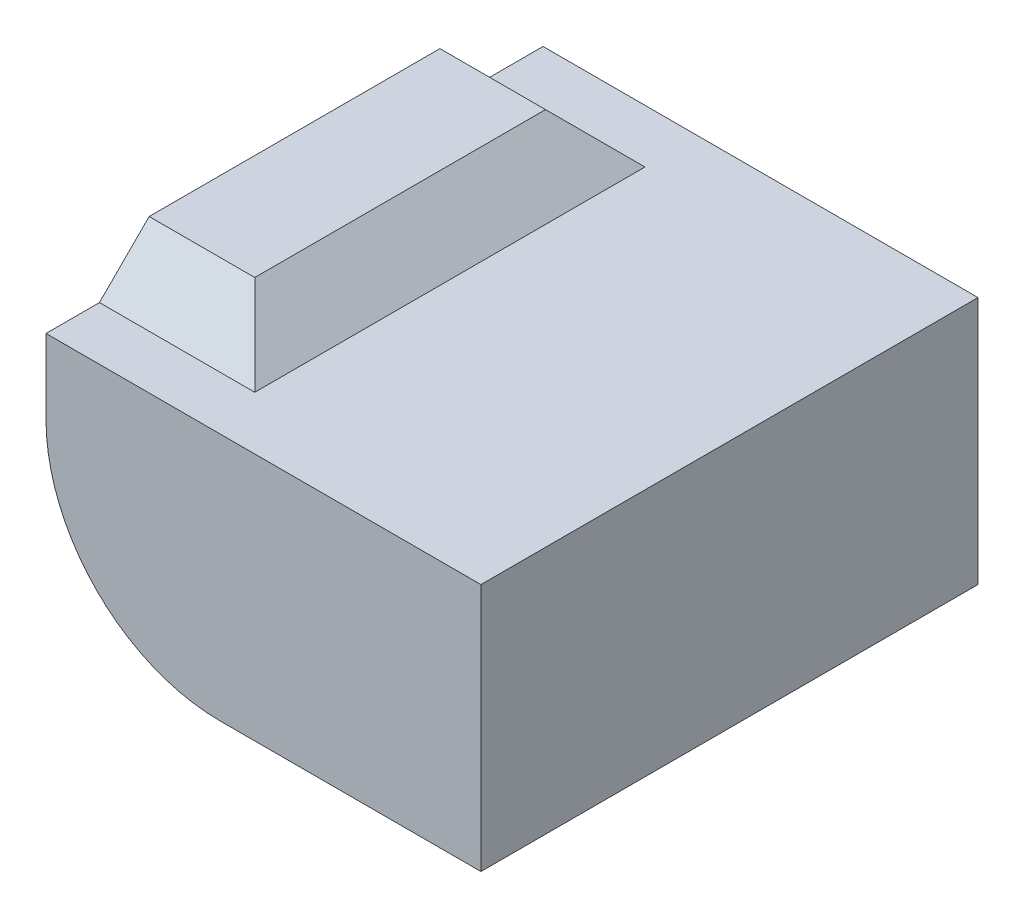
SolidWorks part; units mm, degrees
ref_plane "Front Plane" through (0, 0, 0) normal (0, 0, 1) x (1, 0, 0)
ref_plane "Top Plane" through (0, 0, 0) normal (0, 1, 0) x (1, 0, 0)
ref_plane "Right Plane" through (0, 0, 0) normal (1, 0, 0) x (0, 0, -1)
sketch "Sketch1" plane through (0, 0, 0) normal (0, 0, 1) x (1, 0, 0)
  line L1 (-175, -150) -> (175, -150)
  line L2 (-175, -150) -> (-175, 150)
  line L3 (-175, 150) -> (175, 150)
  line L4 (175, -150) -> (175, 150)
  line L5 (-175, -150) -> (175, 150) construction
  line L6 (-175, 150) -> (175, -150) construction
  point P0 (0, 0)
  dimension "D1" = 350
  dimension "D2" = 300
extrude "Boss-Extrude1" add sketch "Sketch1" along normal blind 117 and the other way blind 117
sketch "Sketch3" plane through (0, 0, 0) normal (0, 0, -1) x (-1, 0, 0)
  line L1 (-175, -150) -> (175, -150)
  line L2 (-175, -150) -> (-175, 150)
  line L3 (-175, 150) -> (175, 150)
  line L4 (175, -150) -> (175, 150)
  line L5 (-175, -150) -> (175, 150) construction
  line L6 (-175, 150) -> (175, -150) construction
  line L7 (175, 150) -> (-75, 150)
  line L8 (175, 150) -> (175, 50)
  line L9 (175, 50) -> (-75, 50)
  line L10 (-75, 150) -> (-75, 50)
  point P0 (0, 0)
  point P9 (0, 0)
  point P13 (0, 0)
  dimension "D2" = 250
  dimension "D3" = 100
extrude "Boss-Extrude2" add sketch "Sketch3" along normal blind 200 and the other way blind 200
sketch "Sketch4" plane through (0, 0, -117) normal (0, 0, -1) x (-1, 0, 0)
  line L0 (175, 150) -> (175, 50) construction
  line L1 (175, 150) -> (-75, 150)
  line L2 (175, 150) -> (175, 90)
  line L3 (175, 90) -> (-75, 90)
  line L4 (-75, 150) -> (-75, 90)
  line L5 (-75, 150) -> (-75, 50) construction
  dimension "D1" = 60
extrude "Cut-Extrude1" cut sketch "Sketch4" against normal blind 540
sketch "Sketch6" plane through (0, 0, -117) normal (0, 0, -1) x (-1, 0, 0)
  line L0 (175, 50) -> (-75, 50) construction
  line L1 (-188.8194, 158.1004) -> (90, 158.1004)
  line L2 (-188.8194, 158.1004) -> (-188.8194, 50)
  line L3 (-188.8194, 50) -> (90, 50)
  line L4 (90, 158.1004) -> (90, 50)
  point P7 (-75, 50)
extrude "Cut-Extrude2" cut sketch "Sketch6" against normal blind 540 and the other way blind 138
chamfer "Chamfer1" distance 40 angle 45 1 edges at (-90, 50, 0)
chamfer "Chamfer2" distance 40 angle 45 2 edges at (-112.5, 50, 117) (-112.5, 50, -117)
fillet "Fillet1" radius 140 1 edges at (-175, -150, 0)
